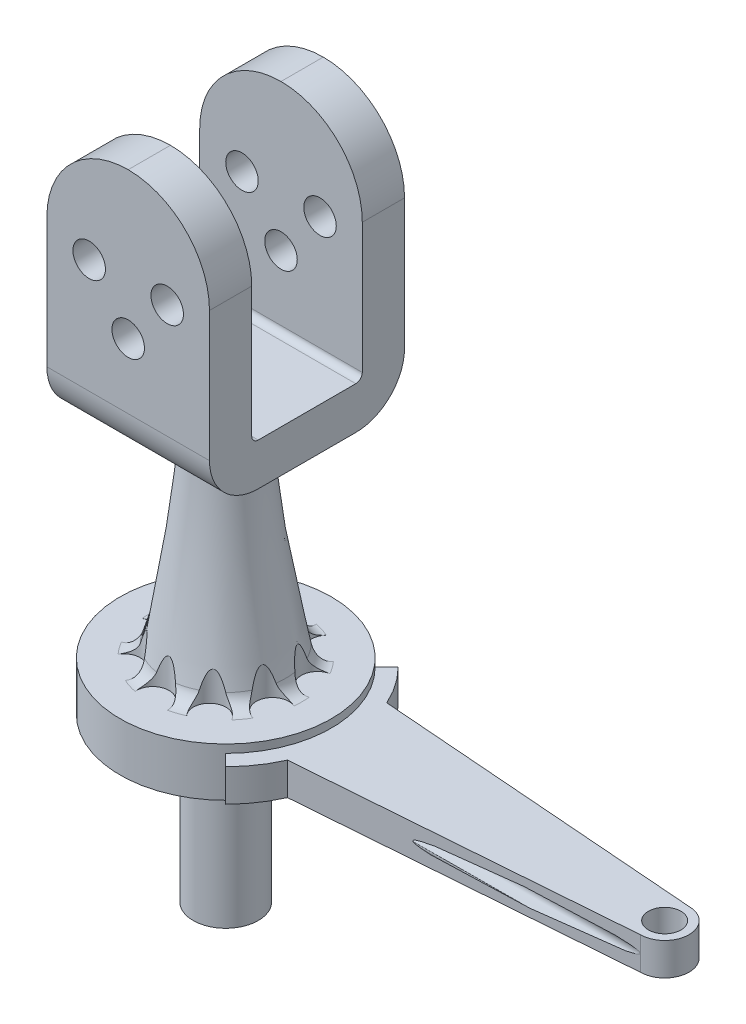
SolidWorks part; units mm, degrees
ref_plane "Front Plane" through (0, 0, 0) normal (0, 0, 1) x (1, 0, 0)
ref_plane "Top Plane" through (0, 0, 0) normal (0, 1, 0) x (1, 0, 0)
ref_plane "Right Plane" through (0, 0, 0) normal (1, 0, 0) x (0, 0, -1)
sketch "Sketch1" plane through (0, 0, 0) normal (1, 0, 0) x (0, 0, -1)
  line L0 (0, 0) -> (0, 130) construction
  line L1 (0, 0) -> (10, 0)
  line L2 (10, 0) -> (10, 50)
  line L3 (10, 50) -> (32.5, 50)
  line L4 (32.5, 50) -> (32.5, 65)
  line L5 (0, 130) -> (10, 130)
  line L6 (32.5, 65) -> (23.4555, 65)
  line L7 (0, 0) -> (0, 130)
  arc A0 (10, 130) -> (18.5836, 68.8757) centre (363.5174, 148.4788) ccw
  arc A1 (18.5836, 68.8757) -> (23.4555, 65) centre (23.4555, 70) ccw
  dimension "D7" = 5
  dimension "D1" = 10
  dimension "D2" = 50
  dimension "D3" = 22.5
  dimension "D4" = 80
  dimension "D5" = 15
  dimension "D6" = 10
revolve "Revolve1" add sketch "Sketch1" angle 360 about L0
sketch "Sketch2" plane through (0, 65, 0) normal (0, 1, 0) x (1, 0, 0)
  line L0 (0, 32.5) -> (0, -32.5) construction
  circle A0 centre (0, 0) radius 32.5 construction
  circle A1 centre (0, 22.4148) radius 5
  point P7 (0, 22.8377)
  point P8 (0, 22.4148)
  dimension "D1" = 10
extrude "Cut-Extrude1" cut sketch "Sketch2" along normal blind 70
pattern_circular "CirPattern1" count 10 over 360 of "Cut-Extrude1"
sketch "Sketch3" plane through (0, 0, 0) normal (1, 0, 0) x (0, 0, -1)
  line L0 (0, 0) -> (0, 210) construction
  line L3 (30, 210) -> (30, 145)
  line L4 (15, 130) -> (-15, 130)
  line L5 (-30, 210) -> (-30, 145)
  line L6 (10, 130) -> (-10, 130) construction
  arc A0 (-15, 130) -> (-30, 145) centre (-15, 145) cw
  arc A1 (15, 130) -> (30, 145) centre (15, 145) ccw
  point P11 (-30, 130)
  point P14 (30, 130)
  dimension "D4" = 15
  dimension "D1" = 60
  dimension "D2" = 80
  dimension "D3" = 30
extrude "Extrude-Thin1" add sketch "Sketch3" along normal mid plane 50 thin thin type one direction reverse wall 13
fillet "Fillet1" radius 25 4 edges at (25, 210, 23.5) (-25, 210, 23.5) (-25, 210, -23.5) (25, 210, -23.5)
sketch "Sketch4" plane through (0, 0, -30) normal (0, 0, -1) x (-1, 0, 0)
  line L0 (0, 210) -> (0, 145) construction
  line L1 (-25, 145) -> (25, 145) construction
  circle A0 centre (0, 165) radius 5
  circle A1 centre (-12, 180) radius 5
  circle A2 centre (12, 180) radius 5
  dimension "D1" = 10
  dimension "D4" = 10
  dimension "D2" = 20
  dimension "D3" = 15
  dimension "D5" = 12
extrude "Cut-Extrude2" cut sketch "Sketch4" against normal blind 112
sketch "Sketch6" plane through (0, 65, 0) normal (0, 1, 0) x (1, 0, 0)
  line L0 (0, 0) -> (32.5, 0) construction
  line L1 (0, 0) -> (22.981, 22.981) construction
  line L2 (0, 0) -> (22.981, -22.981) construction
  arc A0 (22.981, -22.981) -> (22.981, 22.981) centre (0, 0) ccw
  dimension "D1" = 45
extrude "Extrude-Thin2" add sketch "Sketch6" against normal blind 10 from offset 2.5 thin offset against normal yes thin type one direction wall 5
sketch "Sketch7" plane through (0, 62.5, 0) normal (0, 1, 0) x (1, 0, 0)
  line L0 (0, 0) -> (37.5, 0) construction
  line L1 (135, 7.5) -> (34.2561, 15.2567)
  line L2 (135, -7.5) -> (34.2561, -15.2567)
  line L3 (130, 0) -> (135, 0) construction
  arc A0 (135, -7.5) -> (135, 7.5) centre (135, 0) ccw
  circle A1 centre (135, 0) radius 5
  arc A2 (26.5165, -26.5165) -> (26.5165, 26.5165) centre (0, 0) ccw construction
  arc A3 (34.2561, -15.2567) -> (34.2561, 15.2567) centre (0, 0) ccw
  point P10 (0, 0)
  point P13 (33.3072, 17.2303)
  point P15 (33.8545, 16.1283)
  point P16 (34.2561, 15.2567)
  dimension "D2" = 10
  dimension "D3" = 15
  dimension "D1" = 135
extrude "Boss-Extrude1" add sketch "Sketch7" against normal blind 10
sketch "Sketch5" plane through (0, 0, 0) normal (1, 0, 0) x (0, 0, -1)
  line L0 (32.5, 57.5) -> (-32.5, 57.5) construction
  line L1 (32.5, 50) -> (32.5, 65) construction
  line L2 (-32.5, 65) -> (-32.5, 50) construction
  line L3 (0, 50) -> (0, 65) construction
  line L4 (-32.5, 50) -> (32.5, 50) construction
  line L5 (2.3525, 65) -> (-2.3525, 65) construction
  circle A0 centre (10, 57.5) radius 2.5
  circle A1 centre (-10, 57.5) radius 2.5
  dimension "D1" = 5
  dimension "D2" = 10
extrude "Cut-Extrude3" cut sketch "Sketch5" against normal mid plane 386
